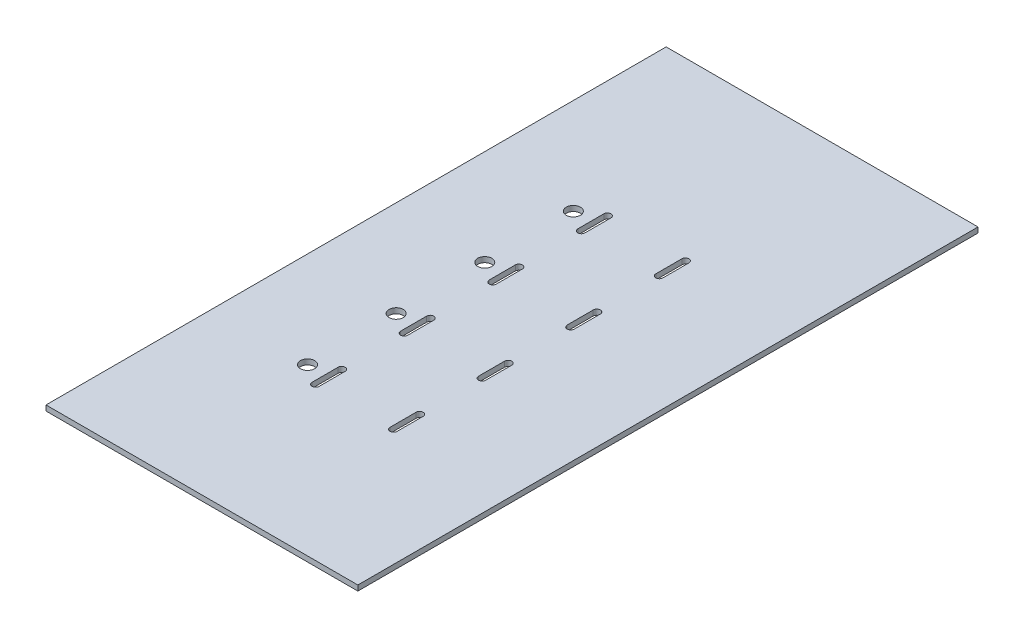
SolidWorks part; units mm, degrees
ref_plane "Front Plane" through (0, 0, 0) normal (0, 0, 1) x (1, 0, 0)
ref_plane "Top Plane" through (0, 0, 0) normal (0, 1, 0) x (1, 0, 0)
ref_plane "Right Plane" through (0, 0, 0) normal (1, 0, 0) x (0, 0, -1)
sketch "Sketch1" plane through (0, 0, 0) normal (0, 1, 0) x (1, 0, 0)
  line L1 (0, 0) -> (176, 0)
  line L2 (0, 0) -> (0, 350)
  line L3 (0, 350) -> (176, 350)
  line L4 (176, 0) -> (176, 350)
  dimension "D1" = 350
  dimension "D2" = 176
extrude "Boss-Extrude1" add sketch "Sketch1" along normal blind 3
sketch "Sketch2" plane through (0, 3, 0) normal (0, 1, 0) x (1, 0, 0)
  line L0 (176, 0) -> (176, 70)
  line L1 (176, 0) -> (176, 350) construction
  line L2 (176, 70) -> (88, 70)
  line L3 (176, 70) -> (176, 120)
  line L4 (176, 120) -> (176, 170)
  line L5 (176, 170) -> (176, 220)
  line L6 (176, 120) -> (88, 120)
  line L7 (176, 170) -> (88, 170)
  line L8 (176, 220) -> (88, 220)
  line L9 (88, 70) -> (88, 93.5)
  line L10 (88, 120) -> (88, 143.5)
  line L11 (88, 170) -> (88, 193.5)
  line L12 (88, 220) -> (88, 243.5)
hole_wizard "Ø4.0mm Dowel Slot1" positions "Sketch6" profile "Sketch7" size "Ø4.0" standard "ANSI Metric" slot yes end condition up to next
sketch "Sketch6" plane through (0, 0, 0) normal (0, -1, 0) x (-1, 0, 0)
  line L0 (-110, 84.15) -> (-110, 102.85) construction
  point P0 (-110, 93.5)
  point P7 (-66, 93.5)
  point P10 (-110, 143.5)
  point P13 (-66, 143.5)
  point P16 (-110, 193.5)
  point P19 (-66, 193.5)
  point P22 (-110, 243.5)
  point P25 (-66, 243.5)
  point P29 (0, 0)
  point P30 (0, 0)
  point P31 (0, 0)
  point P32 (0, 0)
  point P33 (0, 0)
  point P34 (0, 0)
  point P35 (0, 0)
  point P36 (0, 0)
  point P37 (0, 0)
  point P38 (0, 0)
  point P39 (0, 0)
  dimension "D1" = 18.7
sketch "Sketch7" plane through (110, 0, -93.5) normal (1, 0, 0) x (0, 0, -1)
  line L0 (0, 0) -> (0, 3)
  line L1 (0, 3) -> (2, 3)
  line L2 (2, 3) -> (2, 0)
  line L5 (2, 0) -> (0, 0)
  line L11 (0, -6.35) -> (0, 107.95) construction
  dimension "Thru Hole Dia." = 4
  dimension "Thru Hole Depth" = 3
hole_wizard "Ø8.0mm Dowel Hole1" positions "Sketch8" profile "Sketch9" hole size "Ø8.0" standard "AS" end condition up to next
sketch "Sketch8" plane through (0, 3, 0) normal (0, 1, 0) x (1, 0, 0)
  point P0 (54.125, 93.5)
  point P3 (54.125, 143.5)
  point P6 (54.125, 193.5)
  point P9 (54.125, 243.5)
  point P13 (0, 0)
  point P14 (0, 0)
  point P15 (0, 0)
  point P16 (0, 0)
sketch "Sketch9" plane through (54.125, 3, -93.5) normal (1, 0, 0) x (0, 0, 1)
  line L0 (0, 0) -> (0, 3)
  line L1 (0, 3) -> (4, 3)
  line L2 (4, 3) -> (4, 0)
  line L5 (4, 0) -> (0, 0)
  line L11 (0, -6.35) -> (0, 107.95) construction
  dimension "Thru Hole Dia." = 8
  dimension "Thru Hole Depth" = 3
